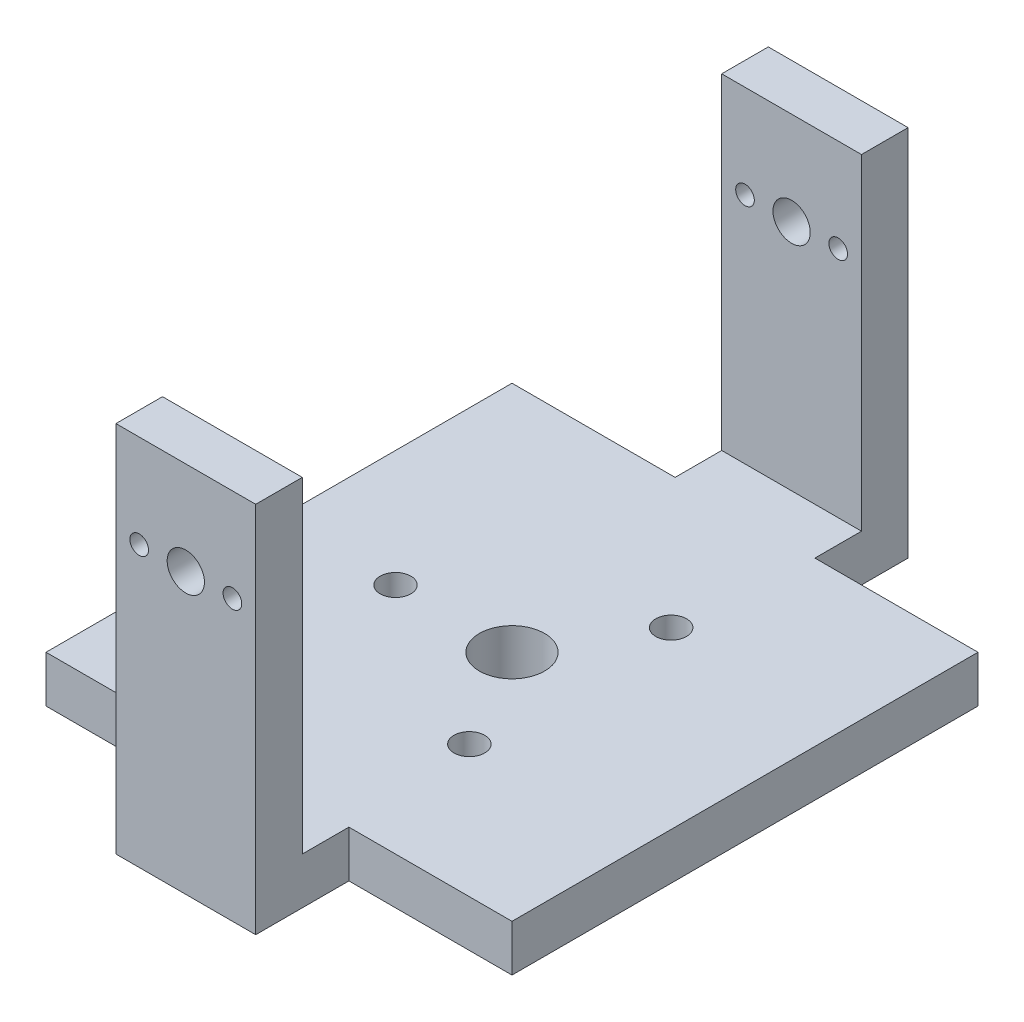
SolidWorks part; units mm, degrees
ref_plane "Plano frontal" through (0, 0, 0) normal (0, 0, 1) x (1, 0, 0)
ref_plane "Plano superior" through (0, 0, 0) normal (0, 1, 0) x (1, 0, 0)
ref_plane "Plano direito" through (0, 0, 0) normal (1, 0, 0) x (0, 0, -1)
sketch "Esboço1" plane through (0, 0, 0) normal (0, 0, 1) x (1, 0, 0)
  line L17 (-15, -50) -> (15, -50)
  line L18 (-15, -50) -> (-15, 20)
  line L19 (-15, 20) -> (15, 20)
  line L20 (15, -50) -> (15, 20)
  line L27 (-15, -50) -> (15, -50)
  line L28 (-15, -50) -> (-15, -60)
  line L29 (-15, -60) -> (15, -60)
  line L30 (15, -50) -> (15, -60)
  line L32 (-50, -50) -> (50, -50)
  line L33 (-50, -50) -> (-50, -60)
  line L34 (-50, -60) -> (50, -60)
  line L35 (50, -50) -> (50, -60)
  circle A0 centre (10, 0) radius 2
  circle A1 centre (-10, 0) radius 2
  circle A2 centre (0, 0) radius 4
extrude "Ressalto-extrusão1" add sketch "Esboço1" along normal blind 10 contours L17 L20 L19 L18 region at (0, -15.5586, 0)
extrude "Ressalto-extrusão3" add sketch "Esboço1<4>" along normal blind 70 contours L30 L17 L28 L29 region at (0, -55, 0)
sketch "Esboço1<4>" plane through (0, 0, 0) normal (0, 0, 1) x (1, 0, 0) same geometry as "Esboço1"
ref_plane "Plano1" through (0, 0, 70) normal (0, 0, 1) x (1, 0, 0)
extrude "Ressalto-extrusão5" add sketch "Esboço1<6>" against normal blind 50 from surface contours L33 L34 L28 L32 | L35 L32 L30 L34 region at (-32.5, -55, 0) region at (32.5, -55, 0) starting at plane "Plano1"
sketch "Esboço1<6>" plane through (0, 0, 0) normal (0, 0, 1) x (1, 0, 0) same geometry as "Esboço1"
mirror "Espelhar2" about plane through (0, 0, 70) normal (0, 0, 1) of "Ressalto-extrusão5", "Ressalto-extrusão3", "Ressalto-extrusão1"
sketch "Esboço3" plane through (0, -50, 0) normal (0, 1, 0) x (1, 0, 0)
  circle A0 centre (0, -70) radius 7
  circle A1 centre (-25, -70) radius 3.3
  circle A2 centre (12.5, -48.3494) radius 3.3
  circle A3 centre (12.5, -91.6506) radius 3.3
  point P11 (0, -70)
  dimension "D1" = 3
extrude "Corte-extrusão1" cut sketch "Esboço3" against normal blind 10 contours A0 | A1 | A3 | A2
